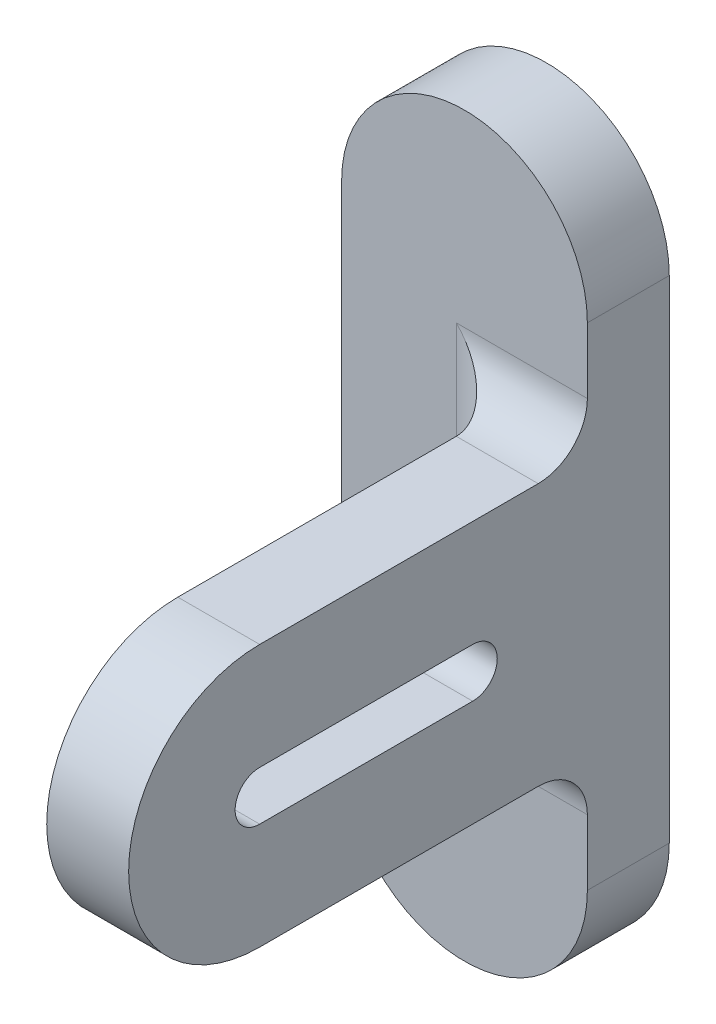
SolidWorks part; units mm, degrees
ref_plane "Спереди" through (0, 0, 0) normal (0, 0, 1) x (1, 0, 0)
ref_plane "Сверху" through (0, 0, 0) normal (0, 1, 0) x (1, 0, 0)
ref_plane "Справа" through (0, 0, 0) normal (1, 0, 0) x (0, 0, -1)
sketch "Эскиз1" plane through (0, 0, 0) normal (0, 0, 1) x (1, 0, 0)
  line L5 (-20.6018, 110.4938) -> (-20.6018, 80.4938) construction
  line L7 (-13.1018, 110.4938) -> (-13.1018, 80.4938)
  line L8 (-28.1018, 110.4938) -> (-28.1018, 80.4938)
  arc A0 (-13.1018, 110.4938) -> (-28.1018, 110.4938) centre (-20.6018, 110.4938) ccw
  arc A1 (-28.1018, 80.4938) -> (-13.1018, 80.4938) centre (-20.6018, 80.4938) ccw
  point P4 (-20.6018, 95.4938)
  dimension "D1" = 30
  dimension "D3" = 15
extrude "Бобышка-Вытянуть1" add sketch "Эскиз1" along normal blind 5
sketch "Эскиз2" plane through (-28.1018, 0, 0) normal (-1, 0, 0) x (0, 0, 1)
  line L0 (5, 110.4938) -> (5, 80.4938) construction
  line L1 (5, 103.4938) -> (25, 103.4938)
  line L2 (5, 103.4938) -> (5, 87.4938)
  line L3 (5, 87.4938) -> (25, 87.4938)
  line L5 (25, 95.4938) -> (12, 95.4938) construction
  line L6 (5, 80.4938) -> (5, 110.4938) construction
  line L7 (25, 93.9938) -> (12, 93.9938)
  line L8 (25, 96.9938) -> (12, 96.9938)
  arc A0 (25, 103.4938) -> (25, 87.4938) centre (25, 95.4938) cw
  arc A1 (25, 93.9938) -> (25, 96.9938) centre (25, 95.4938) ccw
  arc A2 (12, 96.9938) -> (12, 93.9938) centre (12, 95.4938) ccw
  point P7 (5, 95.4938)
  point P10 (18.5, 95.4938)
  point P16 (5, 95.4938)
  dimension "D3" = 3
  dimension "D1" = 20
  dimension "D2" = 16
  dimension "D4" = 7
extrude "Бобышка-Вытянуть2" add sketch "Эскиз2" along normal blind 5 from surface starting at face at (-13.1018, 95.4938, 2.5)
fillet "Скругление1" radius 3 3 edges at (-18.1018, 95.4938, 5) (-15.6018, 87.4938, 5) (-15.6018, 103.4938, 5)
ref_plane "Плоскость1" through (0, 0, 18.5) normal (0, 0, 1) x (1, 0, 0)
ref_plane "Плоскость2" through (0, 95.4938, 0) normal (0, 1, 0) x (1, 0, 0)
ref_axis "Ось1" through (-73.1253, 95.4938, 18.5) along (1, 0, 0)
ref_plane "Плоскость4" through (-24.6018, 0, 0) normal (-1, 0, 0) x (0, 0, 1)
ref_axis "Ось2" through (-24.6018, 120.2438, 18.5) along (0, -1, 0)
